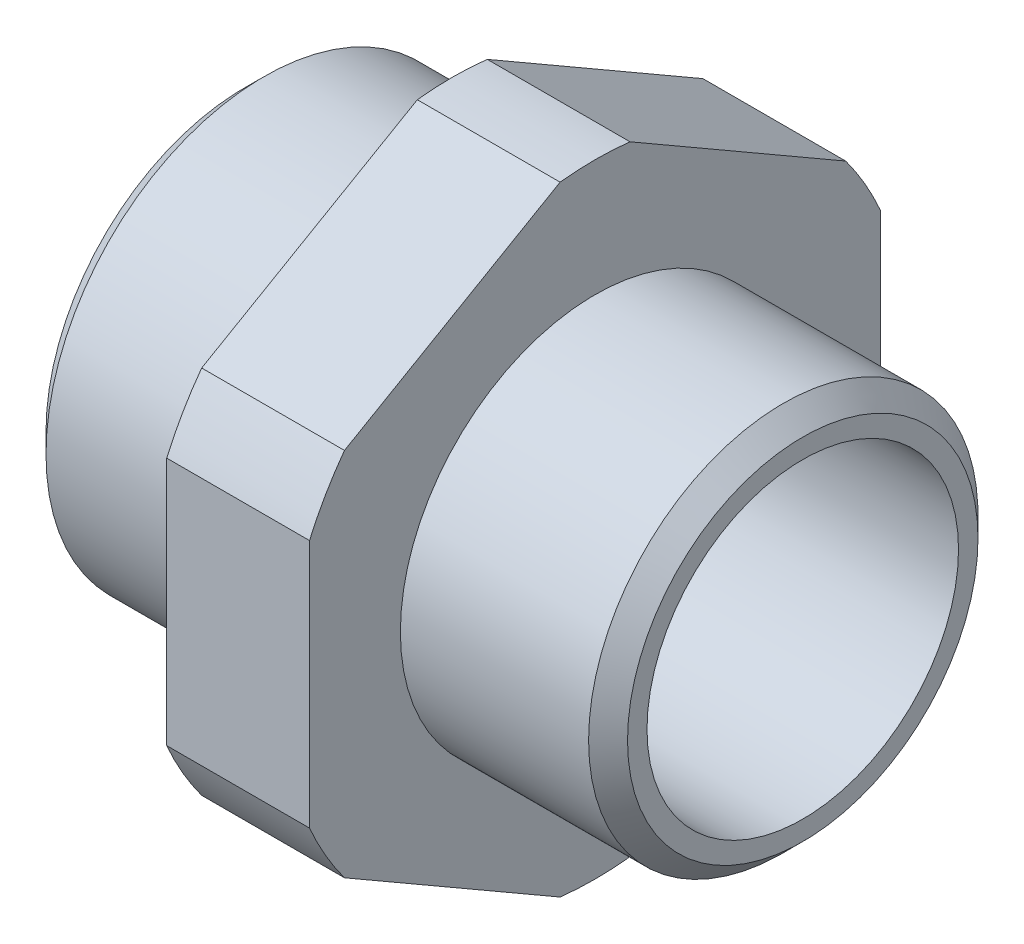
SolidWorks part; units mm, degrees
note: '?' marks a value the reader was unsure of.
ref_plane "Спереди" through (0, 0, 0) normal (0, 0, 1) x (1, 0, 0)
ref_plane "Сверху" through (0, 0, 0) normal (0, 1, 0) x (1, 0, 0)
ref_plane "Справа" through (0, 0, 0) normal (1, 0, 0) x (0, 0, -1)
sketch "Эскиз2" plane through (0, 0, 0) normal (1, 0, 0) x (0, 0, -1)
  circle A0 centre (0, 0) radius 7.5
  dimension "D1" = 15
extrude "Вытянуть1" add sketch "Эскиз2" against normal blind 8
sketch "Эскиз3" plane through (-8, 0, 0) normal (-1, 0, 0) x (0, 0, 1)
  line L0 (0, 12.7017) -> (-11, 6.3509)
  line L1 (-11, 6.3509) -> (-11, -6.3509)
  line L2 (-11, -6.3509) -> (0, -12.7017)
  line L3 (0, -12.7017) -> (11, -6.3509)
  line L4 (11, -6.3509) -> (11, 6.3509)
  line L5 (11, 6.3509) -> (0, 12.7017)
  circle A0 centre (0, 0) radius 12.7017
  circle M8 centre (0, 0) radius 7.5
  dimension "D1" = 120
  dimension "D2" = 22
extrude "Вытянуть2" add sketch "Эскиз3" along normal blind 5.5 contours L4 L5 L0 L1 L2 L3 M8 | M8
sketch "Эскиз4" plane through (-13.5, 0, 0) normal (-1, 0, 0) x (0, 0, 1)
  circle A0 centre (0, 0) radius 8.4
  dimension "D1" = 16.8
extrude "Вытянуть3" add sketch "Эскиз4" along normal blind 8
ref_axis "Ось1" through (5.6571, 0, 0) along (-1, 0, 0)?
sketch "Эскиз5" plane through (0, 0, 0) normal (0, 0, 1) x (1, 0, 0)
  line L0 (0, 0) -> (0, 6)
  line L2 (0, -7.5) -> (0, 7.5) construction
  line L3 (0, 6) -> (-12, 6)
  line L4 (-15, 6.5) -> (-13.5, 5)
  line L5 (-15, 6.5) -> (-21.5, 6.5)
  line L6 (-21.5, 8.4) -> (-21.5, -8.4) construction
  line L7 (-21.5, 6.5) -> (-21.5, 0)
  line L8 (-21.5, 0) -> (0, 0)
  line L9 (-21.5, 0) -> (-21.5, -6.5) construction
  line L10 (-21.5, -6.5) -> (-15, -6.5) construction
  line L11 (-13.5, 5) -> (-12, 5)
  line L12 (-12, -6) -> (0, -6) construction
  line L13 (0, -6) -> (0, 0) construction
  line L14 (-12, 5) -> (-12, 6)
  line L15 (-12, -6) -> (-12, -5) construction
  line L16 (-12, -5) -> (-13.5, -5) construction
  line L17 (-13.5, -5) -> (-15, -6.5) construction
  dimension "D1" = 13
  dimension "D2" = 10
  dimension "D3" = 12
  dimension "D4" = 12
  dimension "D5" = 6.5
  dimension "D6" = 45
revolve "Вырез-Повернуть1" cut sketch "Эскиз5" angle 360 about L8
sketch "Эскиз6" plane through (-13.5, 0, 0) normal (-1, 0, 0) x (0, 0, 1)
  circle A0 centre (0, 0) radius 12.7017
  circle A1 centre (0, 0) radius 12
  dimension "D1" = 24
extrude "Вырез-Вытянуть1" cut sketch "Эскиз6" against normal through all
chamfer "Фаска1" distance 0.75 angle 45 2 edges at (-21.5, 0, 8.4) (0, 0, -7.5)
sketch "Эскиз7" plane through (-12, 0, 0) normal (1, 0, 0) x (0, 0, -1)
  line L1 (-0.5, 0) -> (0.5, 0)
  line L2 (-0.5, 0) -> (-0.5, 6.5)
  line L3 (-0.5, 6.5) -> (0.5, 6.5)
  line L4 (0.5, 0) -> (0.5, 6.5)
  circle A0 centre (0, 0) radius 6.5 construction
  point P4 (0, 0)
  dimension "D1" = 1
extrude "Вытянуть4" add sketch "Эскиз7" against normal up to surface (9.5 mm away) up to face at (-21.5, 0, 7.65)
sketch "Эскиз8" plane through (-21.5, 0, 0) normal (-1, 0, 0) x (0, 0, 1)
  circle A0 centre (0, 0) radius 5
  arc A1 (-0.5, 4.9749) -> (0.5, 4.9749) centre (0, 0) ccw construction
extrude "Вырез-Вытянуть2" cut sketch "Эскиз8" against normal through all
sketch "Эскиз9" plane through (-21.5, 0, 0) normal (-1, 0, 0) x (0, 0, 1)
  circle A0 centre (0, 0) radius 6.5
  arc A1 (-0.5, 6.4807) -> (0.5, 6.4807) centre (0, 0) ccw construction
extrude "Вырез-Вытянуть3" cut sketch "Эскиз9" against normal blind 6.5
pattern_circular "Круговой массив1" count 6 over 360 about axis through (0, 0, 0) along (1, 0, 0) of "Вытянуть4", "Вырез-Вытянуть2", "Вырез-Вытянуть3"
